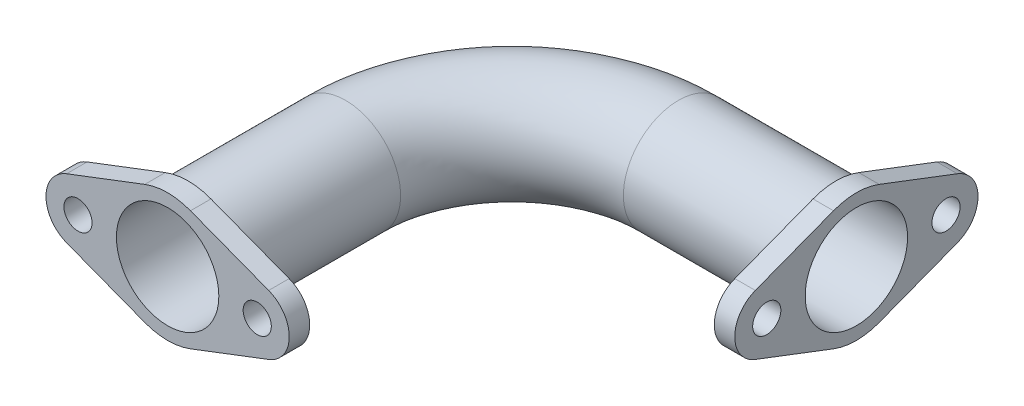
SolidWorks part; units mm, degrees
ref_plane "Front Plane" through (0, 0, 0) normal (0, 0, 1) x (1, 0, 0)
ref_plane "Top Plane" through (0, 0, 0) normal (0, 1, 0) x (1, 0, 0)
ref_plane "Right Plane" through (0, 0, 0) normal (1, 0, 0) x (0, 0, -1)
sketch "Sketch1" plane through (0, 0, 0) normal (0, 1, 0) x (1, 0, 0)
  line L2 (43.5, 126.5) -> (105, 126.5)
  line L3 (-21.5, 0) -> (-21.5, 61.5)
  arc A1 (43.5, 126.5) -> (-21.5, 61.5) centre (43.5, 61.5) ccw
sweep "Sweep3" add path "Sketch1" circular profile diameter 43 parameters "D3"=43
sweep "Cut-Sweep1" cut path "Sketch1<5>" circular profile diameter 40 parameters "D3"=40
sketch "Sketch1<5>" plane through (0, 0, 0) normal (0, 1, 0) x (1, 0, 0) same geometry as "Sketch1"
sketch "Sketch23" plane through (105, 0, 0) normal (1, 0, 0) x (0, 0, -1)
  line L0 (126.5, 62.448) -> (126.5, -54.6782) construction
  line L1 (97.1366, 0) -> (183.7432, 0) construction
  line L2 (87.0357, 11.6756) -> (117.5714, 23.3512)
  line L3 (87.0357, -11.6756) -> (117.5714, -23.3512)
  line L4 (165.9643, -11.6756) -> (135.4286, -23.3512)
  line L5 (165.9643, 11.6756) -> (135.4286, 23.3512)
  circle A0 centre (126.5, 0) radius 21.5
  circle A1 centre (126.5, 0) radius 20
  arc A2 (117.5714, -23.3512) -> (135.4286, -23.3512) centre (126.5, 0) ccw
  circle A4 centre (91.5, 0) radius 5.5
  arc A5 (87.0357, 11.6756) -> (87.0357, -11.6756) centre (91.5, 0) ccw
  circle A7 centre (161.5, 0) radius 5.5
  arc A8 (165.9643, 11.6756) -> (165.9643, -11.6756) centre (161.5, 0) cw
  arc A9 (135.4286, 23.3512) -> (117.5714, 23.3512) centre (126.5, 0) ccw
  circle M15 centre (126.5, 0) radius 20
  circle M16 centre (126.5, 0) radius 21.5
  dimension "D1" = 50
  dimension "D2" = 11
  dimension "D3" = 25
  dimension "D4" = 35
extrude "Boss-Extrude2" add sketch "Sketch23" along normal blind 8 contours L5 A9 L2 A5 L3 A2 L4 A8 A7 A4 M16 | M16 M15 region at (105, 16.5107, -102.687) region at (105, 0, -105.6081)
sketch "Sketch26" plane through (0, 0, 0) normal (0, 0, 1) x (1, 0, 0)
  line L0 (-60.9643, 11.6756) -> (-30.4286, 23.3512)
  line L1 (-60.9643, -11.6756) -> (-30.4286, -23.3512)
  line L2 (17.9643, -11.6756) -> (-12.5714, -23.3512)
  line L3 (17.9643, 11.6756) -> (-12.5714, 23.3512)
  circle A1 centre (-21.5, 0) radius 21.5
  circle A2 centre (-21.5, 0) radius 20
  arc A3 (-30.4286, -23.3512) -> (-12.5714, -23.3512) centre (-21.5, 0) ccw
  circle A4 centre (-56.5, 0) radius 5.5
  arc A5 (-60.9643, 11.6756) -> (-60.9643, -11.6756) centre (-56.5, 0) ccw
  circle A6 centre (13.5, 0) radius 5.5
  arc A7 (17.9643, 11.6756) -> (17.9643, -11.6756) centre (13.5, 0) cw
  arc A8 (-12.5714, 23.3512) -> (-30.4286, 23.3512) centre (-21.5, 0) ccw
  circle M11 centre (-21.5, 0) radius 20
  circle M12 centre (-21.5, 0) radius 21.5
  dimension "D1" = 50
extrude "Boss-Extrude3" add sketch "Sketch26" along normal blind 8 contours L3 A8 L0 A5 L1 A3 L2 A7 A6 A4 M12 | M12 M11 region at (-45.313, 16.5107, 0) region at (-42.3919, 0, 0)
